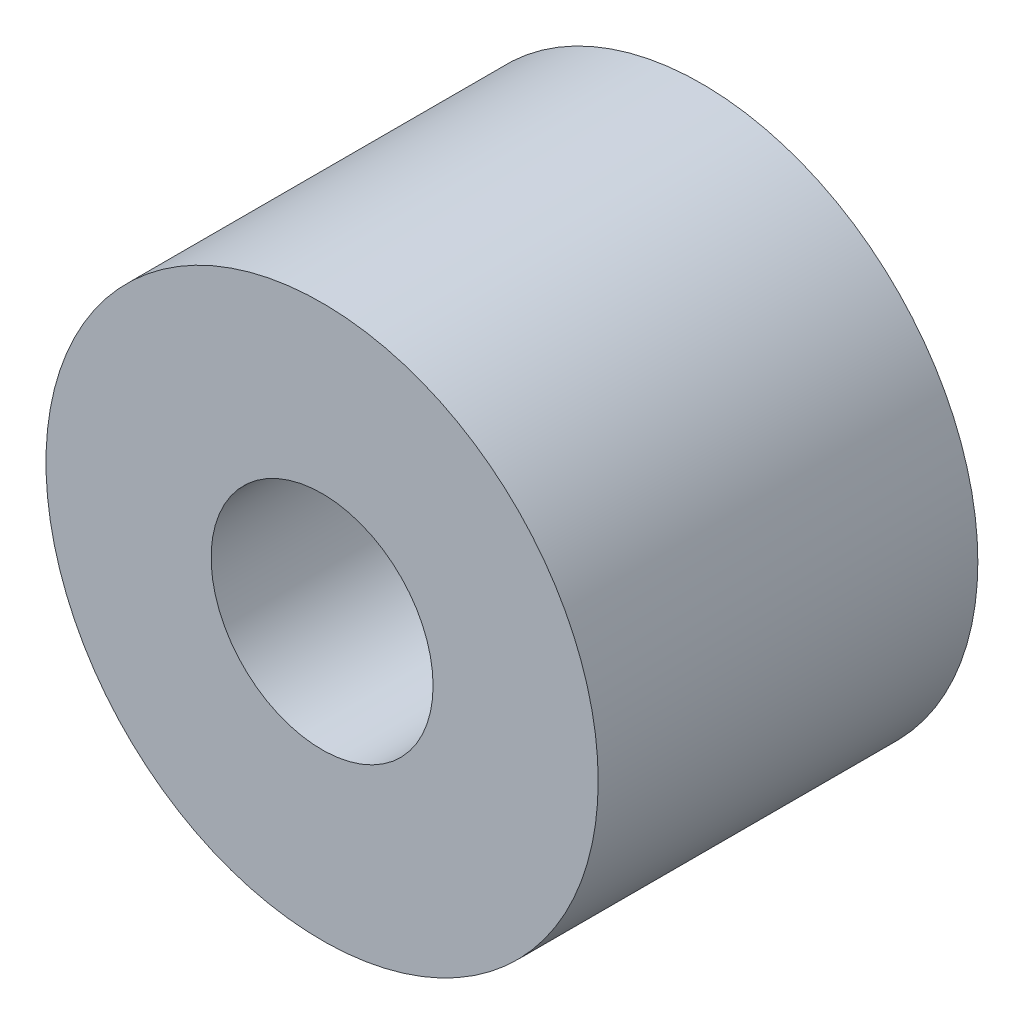
SolidWorks part; units mm, degrees
ref_plane "Front Plane" through (0, 0, 0) normal (0, 0, 1) x (1, 0, 0)
ref_plane "Top Plane" through (0, 0, 0) normal (0, 1, 0) x (1, 0, 0)
ref_plane "Right Plane" through (0, 0, 0) normal (1, 0, 0) x (0, 0, -1)
sketch "Sketch1" plane through (0, 0, 0) normal (0, 0, 1) x (1, 0, 0)
  circle A0 centre (0, 0) radius 6.35
  dimension "D1" = 12.7
extrude "Boss-Extrude1" add sketch "Sketch1" along normal mid plane 8.7312
sketch "Sketch2" plane through (0, 0, 4.3656) normal (0, 0, 1) x (1, 0, 0)
  point P0 (0, 0)
  point P3 (0, 0)
hole_wizard "Tap Drill for 1/4-20 Tap1" positions "Sketch2" profile "Sketch3" hole size "1/4-20" standard "ANSI Inch" end condition through all
sketch "Sketch3" plane through (0, 0, 4.3656) normal (1, 0, 0) x (0, -1, 0)
  line L0 (0, 0) -> (0, 8.7312)
  line L1 (0, 8.7312) -> (2.5527, 8.7312)
  line L2 (2.5527, 8.7312) -> (2.5527, 0)
  line L5 (2.5527, 0) -> (0, 0)
  line L11 (0, -6.35) -> (0, 107.95) construction
  dimension "Thru Hole Dia." = 5.1054
  dimension "Thru Hole Depth" = 8.7312
cosmetic thread "Cosmetic Thread1" parameters "D2"=6.1054
equation "\"AIRFRAME_OD\"= 3.091in"
equation "\"AIRFRAME_ID\"= 3.00in"
equation "\"FLAT_T\"= 0.125in"
equation "\"NOSE_EXP_L\"= 3.5in"
equation "\"NOSE_SHOULDER_L\"= 5in"
equation "\"MAIN_L\"= 30in"
equation "\"RECO_COUP_L\"= 6in"
equation "\"RECO_SWITCH_L\"= 1.5in"
equation "\"DROGUE_L\"= 14in"
equation "\"ATS_FORE_COUP_L\"= 4in"
equation "\"ATS_AFT_COUP_L\"= 4in"
equation "\"LOWER_L\"= 16in"
equation "\"FIN_N\"= 4"
equation "\"CR_AFT_X\"= 0.5in"
equation "\"CR_FORE_X\"= 6in"
